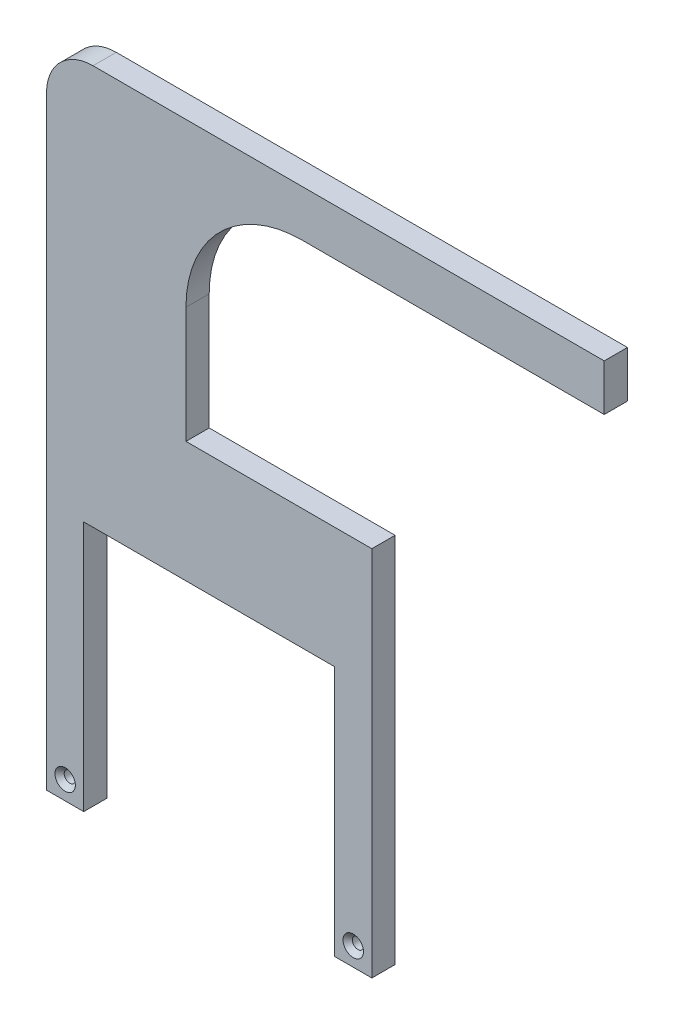
SolidWorks part; units mm, degrees
ref_plane "Plan de face" through (0, 0, 0) normal (0, 0, 1) x (1, 0, 0)
ref_plane "Plan de dessus" through (0, 0, 0) normal (0, 1, 0) x (1, 0, 0)
ref_plane "Plan de droite" through (0, 0, 0) normal (1, 0, 0) x (0, 0, -1)
sketch "Esquisse1" plane through (0, 0, 0) normal (0, 0, 1) x (1, 0, 0)
  line L36 (0, 0) -> (0, 140)
  line L41 (0, 140) -> (120, 140)
  line L42 (120, 140) -> (120, 130)
  line L43 (120, 130) -> (30, 130)
  line L44 (30, 130) -> (30, 80)
  line L45 (30, 80) -> (70, 80)
  line L46 (70, 80) -> (70, 0)
  line L47 (70, 0) -> (62, 0)
  line L48 (62, 0) -> (62, 54)
  line L49 (62, 54) -> (8, 54)
  line L50 (0, 0) -> (8, 0)
  line L51 (8, 0) -> (8, 54)
  point P3 (0, 0)
  point P4 (0, 0)
  point P5 (0, 148.6603)
  point P10 (0, 0)
  point P17 (0, 0)
  point P18 (0, 0)
  dimension "D2" = 8
  dimension "D3" = 54
  dimension "D4" = 8
  dimension "D5" = 10
  dimension "D6" = 140
  dimension "D8" = 120
  dimension "D10" = 90
  dimension "D11" = 50
  dimension "D12" = 54
extrude "Boss.-Extru.1" add sketch "Esquisse1" along normal blind 5
sketch "Esquisse2" plane through (0, 0, 5) normal (0, 0, 1) x (1, 0, 0)
  line L0 (0, 0) -> (8, 0) construction
  line L1 (8, 0) -> (8, 54) construction
  line L2 (62, 0) -> (70, 0) construction
  line L3 (70, 0) -> (70, 80) construction
  circle A0 centre (4, 4) radius 1
  circle A1 centre (66, 4) radius 1
  dimension "D1" = 4
  dimension "D3" = 2
  dimension "D6" = 2
  dimension "D2" = 4
  dimension "D4" = 4
  dimension "D5" = 4
hole_wizard "Fraisage pour vis à tête fraisée M21" positions "Esquisse3" profile "Esquisse4" countersink size "M2" standard "ISO" end condition through all
sketch "Esquisse3" plane through (0, 0, 5) normal (0, 0, 1) x (1, 0, 0)
  point P0 (4, 4)
  point P3 (66, 4)
sketch "Esquisse4" plane through (4, 4, 5) normal (1, 0, 0) x (0, -1, 0)
  line L0 (0, 0) -> (0, 5)
  line L1 (0, 5) -> (1.2, 5)
  line L2 (1.2, 5) -> (1.2, 1)
  line L3 (1.2, 1) -> (2.2, 0)
  line L5 (2.2, 0) -> (0, 0)
  line L6 (-1.2, 1) -> (-2.2, 0) construction
  line L11 (0, -6.35) -> (0, 107.95) construction
  dimension "Diamètre du perçage jusqu'au prochain" = 2.4
  dimension "Profondeur du perçage jusqu'au prochain" = 5
  dimension "Diamètre du fraisage entrant" = 4.4
  dimension "Angle du fraisage entrant" = 90
fillet "Congé1" radius 10 1 edges at (0, 140, 2.5)
fillet "Congé2" radius 25 1 edges at (30, 130, 2.5)
